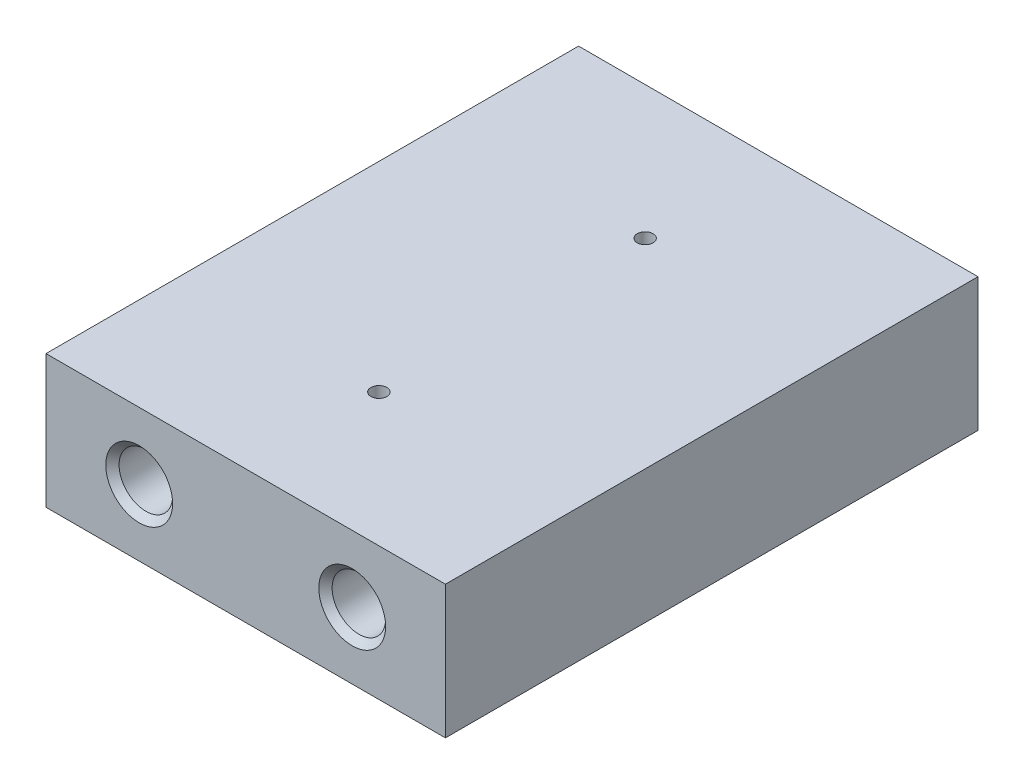
SolidWorks part; units mm, degrees
material "6063-T5"
ref_plane "Front Plane" through (0, 0, 0) normal (0, 0, 1) x (1, 0, 0)
ref_plane "Top Plane" through (0, 0, 0) normal (0, 1, 0) x (1, 0, 0)
ref_plane "Right Plane" through (0, 0, 0) normal (1, 0, 0) x (0, 0, -1)
sketch "Sketch1" plane through (0, 0, 0) normal (0, 0, 1) x (1, 0, 0)
  line L1 (-19.05, -6.35) -> (19.05, -6.35)
  line L2 (-19.05, -6.35) -> (-19.05, 6.35)
  line L3 (-19.05, 6.35) -> (19.05, 6.35)
  line L4 (19.05, -6.35) -> (19.05, 6.35)
  line L5 (-19.05, -6.35) -> (19.05, 6.35) construction
  line L6 (-19.05, 6.35) -> (19.05, -6.35) construction
  point P0 (0, 0)
  dimension "D1" = 38.1
  dimension "D2" = 12.7
extrude "Boss-Extrude1" add sketch "Sketch1" against normal blind 50.8
sketch "Sketch2" plane through (0, 0, 0) normal (0, 0, 1) x (1, 0, 0)
  line L1 (0, -1000) -> (0, 49000) construction
  point P0 (-10.16, 0)
  point P1 (10.16, 0)
  dimension "D1" = 20.32
hole_wizard "1/4-20 Tapped Hole1" positions "3DSketch1" profile "Sketch4" tap size "1/4-20" standard "ANSI Inch"
sketch3d "3DSketch1"
  point P0 (-10.16, 0, 0)
  point P3 (10.16, 0, 0)
sketch "Sketch4" plane through (-10.16, 0, 0) normal (1, 0, 0) x (0, -1, 0)
  line L0 (0, 0) -> (0, 14.2338)
  line L1 (0, 14.2338) -> (2.5527, 12.7)
  line L2 (2.5527, 12.7) -> (2.5527, 0.635)
  line L3 (2.5527, 0.635) -> (3.1877, 0)
  line L5 (3.1877, 0) -> (0, 0)
  line L6 (-2.5527, 0.635) -> (-3.1877, 0) construction
  line L10 (0, 14.2338) -> (-2.5527, 12.7) construction
  line L11 (0, -6.35) -> (0, 107.95) construction
  dimension "Tap Drill Dia." = 5.1054
  dimension "Tap Drill Depth" = 12.7
  dimension "Near C'Sink Dia." = 6.3754
  dimension "Near C'Sink Angle" = 90
  dimension "Drill Angle" = 118
cosmetic thread "Hole Thread1" parameters "D1"=10.16, "D2"=6.35
cosmetic thread "Hole Thread2" parameters "D1"=10.16, "D2"=6.35
ref_plane "Plane1" through (0, 0, -25.4) normal (0, 0, 1) x (1, 0, 0)
mirror "Mirror1" about plane through (0, 0, -25.4) normal (0, 0, 1) of "1/4-20 Tapped Hole1"
sketch "Sketch5" plane through (0, 6.35, 0) normal (0, 1, 0) x (1, 0, 0)
  line L0 (0, -1000) -> (0, 49000) construction
  line L1 (-999.1252, 25.4) -> (49000.8748, 25.4) construction
  line L3 (19.05, 0) -> (-19.05, 0) construction
  line L4 (19.05, 50.8) -> (-19.05, 50.8) construction
  point P4 (0, 38.1)
  point P6 (0, 12.7)
  dimension "D1" = 25.4
hole_wizard "#1-64 Tapped Hole1" positions "3DSketch2" profile "Sketch7" tap size "#1-64" standard "ANSI Inch" end condition through all
sketch3d "3DSketch2"
  point P0 (0, 6.35, -38.1)
  point P3 (0, 6.35, -12.7)
sketch "Sketch7" plane through (0, 6.35, -38.1) normal (1, 0, 0) x (0, 0, 1)
  line L0 (0, 0) -> (0, 12.7)
  line L1 (0, 12.7) -> (0.7556, 12.7)
  line L2 (0.7556, 12.7) -> (0.7556, 0)
  line L5 (0.7556, 0) -> (0, 0)
  line L11 (0, -6.35) -> (0, 107.95) construction
  dimension "Thru Tap Drill Dia." = 1.5113
  dimension "Thru Tap Drill Depth" = 12.7
cosmetic thread "Hole Thread3" parameters "D2"=1.8542
cosmetic thread "Hole Thread4" parameters "D2"=1.8542
sketch "Sketch11" plane through (-19.05, 0, 0) normal (-1, 0, 0) x (0, 0, 1)
  line L0 (-1048.0986, 0) -> (48951.9014, 0) construction
  line L1 (-25.4, -1002.8477) -> (-25.4, 48997.1523) construction
  line L2 (-25.4, -6.985) -> (-25.4, 6.985) construction
  line L3 (201000, 6.35) -> (-249000, 6.35) construction
  line L4 (-50.8, -6.35) -> (0, -6.35) construction
  point P10 (-34.29, 0)
  point P11 (-16.51, 0)
  dimension "D1" = 17.78
hole_wizard "1/8 (0.125) Diameter Hole1" positions "Sketch12" profile "Sketch13" hole size "1/8" standard "ANSI Inch"
sketch "Sketch12" plane through (-19.05, 0, 0) normal (-1, 0, 0) x (0, 0, 1)
  point P0 (-34.29, 0)
  point P3 (-16.51, 0)
sketch "Sketch13" plane through (-19.05, 0, -34.29) normal (0, 1, 0) x (0, 0, 1)
  line L0 (0, 0) -> (0, 6.0339)
  line L1 (0, 6.0339) -> (1.5875, 5.08)
  line L2 (1.5875, 5.08) -> (1.5875, 0)
  line L5 (1.5875, 0) -> (0, 0)
  line L10 (0, 6.0339) -> (-1.5875, 5.08) construction
  line L11 (0, -6.35) -> (0, 107.95) construction
  dimension "Hole Dia." = 3.175
  dimension "Hole Depth" = 5.08
  dimension "Drill Angle" = 118
